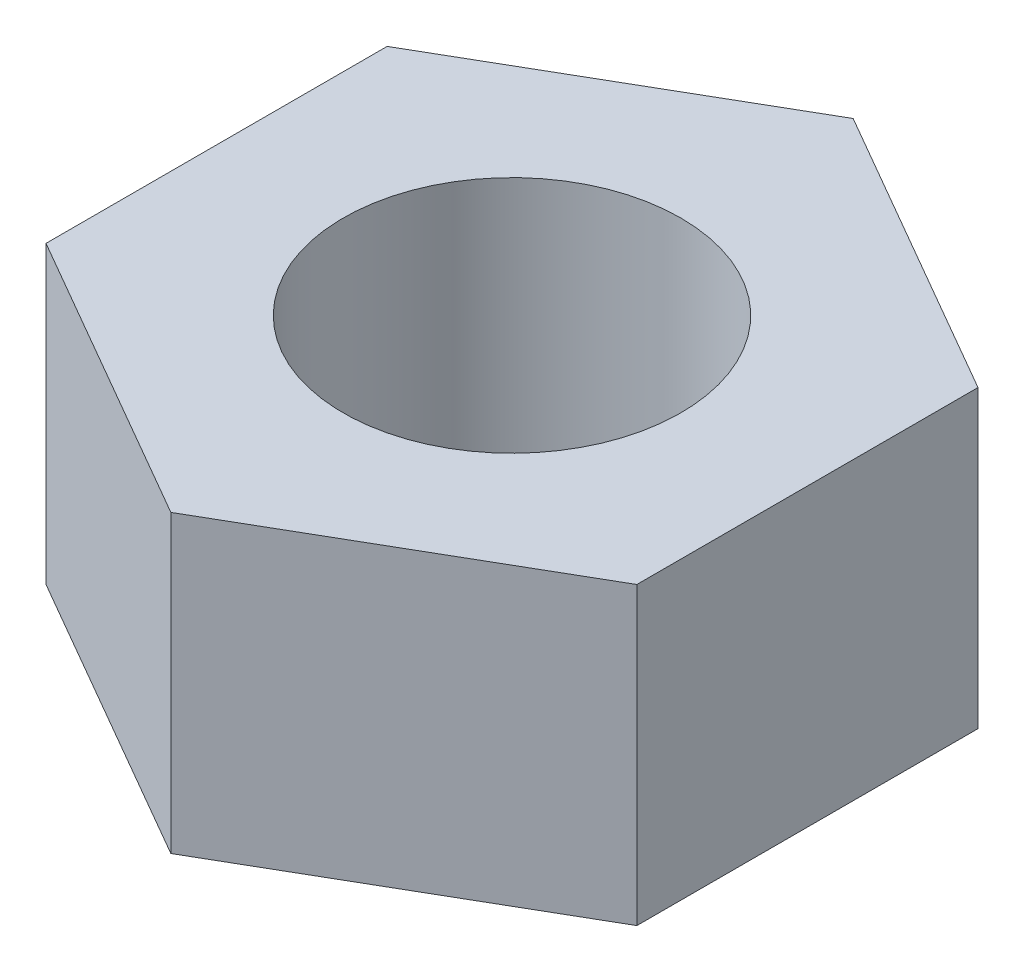
SolidWorks part; units mm, degrees
material "AISI 4130 Steel, normalized at 870C"
ref_plane "Front Plane" through (0, 0, 0) normal (0, 0, 1) x (1, 0, 0)
ref_plane "Top Plane" through (0, 0, 0) normal (0, 1, 0) x (1, 0, 0)
ref_plane "Right Plane" through (0, 0, 0) normal (1, 0, 0) x (0, 0, -1)
sketch "Sketch1" plane through (0, 0, 0) normal (0, 0, 1) x (1, 0, 0)
  line L0 (0, -2.7781) -> (0, 2.7781) construction
  line L1 (5.5562, 0) -> (-5.5562, 0) construction
  line L2 (3.175, -2.7781) -> (-3.175, -2.7781) construction
  line L3 (3.175, -2.7781) -> (3.175, -1.5081) construction
  point P4 (0, 0)
  point P8 (0, 0)
  point P11 (0, -2.7781)
  dimension "Height" = 5.5562
  dimension "Width" = 11.1125
  dimension "Thread Size" = 6.35
  dimension "Thread Pitch" = 1.27
sketch "Sketch2" plane through (0, 0, 0) normal (1, 0, 0) x (0, 0, -1)
  line L0 (0, -2.7781) -> (0, 2.7781) construction
  line L1 (3.048, -3.3433) -> (-3.048, -3.3433)
  line L2 (3.048, -3.3433) -> (3.048, 2.7781)
  line L3 (3.048, 2.7781) -> (-3.048, 2.7781)
  line L4 (-3.048, -3.3433) -> (-3.048, 2.7781)
  line L5 (3.048, -3.3433) -> (-3.048, 2.7781) construction
  line L6 (3.048, 2.7781) -> (-3.048, -3.3433) construction
  point P0 (0, -0.2826)
  point P7 (0, 2.7781)
  dimension "Minimum Slot Width" = 6.096
  dimension "Minimum Slot Depth" = 6.1214
sketch "Sketch11" plane through (0, 0, 0) normal (0, 1, 0) x (1, 0, 0)
  line L1 (0, 6.4158) -> (-5.5562, 3.2079)
  line L2 (-5.5562, 3.2079) -> (-5.5562, -3.2079)
  line L3 (-5.5562, -3.2079) -> (0, -6.4158)
  line L4 (0, -6.4158) -> (5.5562, -3.2079)
  line L5 (5.5562, -3.2079) -> (5.5562, 3.2079)
  line L6 (5.5562, 3.2079) -> (0, 6.4158)
  circle A0 centre (0, 0) radius 5.5563 construction
  circle A1 centre (0, 0) radius 3.175
  point P19 (0, -3.175)
extrude "Boss-Extrude1" add sketch "Sketch11" along normal up to vertex (2.7781 mm away) and the other way up to vertex (2.7781 mm away) up to point (0, 2.7781, 0) other way up to point (0, -2.7781, 0)
fillet "Fillet1" [suppressed] radius 0.3334
sketch "Sketch3" plane through (0, 0, 0) normal (1, 0, 0) x (0, 0, -1)
  line L1 (3.2079, 2.7781) -> (6.4158, 2.7781) construction
  line L2 (5.0006, -2.7781) -> (6.4158, -1.9611)
  line L3 (3.2079, -2.7781) -> (6.4158, -2.7781) construction
  line L4 (6.4158, 2.7781) -> (6.4158, -2.7781) construction
  line L5 (6.4158, -1.9611) -> (6.4158, -2.7781)
  line L7 (5.1118, 2.7781) -> (6.4158, 2.0252)
  line L8 (6.4158, 2.0252) -> (6.4158, 2.7781)
  line L10 (5.0006, -2.7781) -> (6.4158, -2.7781)
  line L12 (5.1118, 0) -> (5.5563, 0) construction
  line L16 (5.1118, 2.7781) -> (6.4158, 2.7781)
  line L21 (3.175, -2.7781) -> (3.175, -2.6194)
  line L22 (-3.2079, -2.7781) -> (3.2079, -2.7781) construction
  line L24 (3.3338, -2.7781) -> (3.175, -2.7781)
  line L25 (3.175, -2.6194) -> (3.3338, -2.7781)
  line L26 (3.175, 2.7781) -> (3.175, 2.6194)
  line L27 (3.175, 2.7781) -> (3.3338, 2.7781)
  line L28 (3.3338, 2.7781) -> (3.175, 2.6194)
  line L29 (3.048, 2.7781) -> (-3.048, 2.7781) construction
  line L30 (3.3338, 0) -> (3.7783, 0) construction
  line L31 (4.6673, 0) -> (5.1118, 0) construction
  line L32 (3.7783, 0) -> (4.2228, 0) construction
  line L33 (4.2228, 0) -> (4.6673, 0) construction
  point P0 (5.1118, 2.7781)
  point P1 (5.5563, 0)
  point P14 (3.175, 0)
  point P36 (5.5563, -2.7781)
  point P44 (5.334, 0)
  dimension "D2" = 30
  dimension "D5" = 0.1588
  dimension "D7" = 0.5556
  dimension "D1" = 30
revolve "Cut-Revolve2" [suppressed] cut sketch "Sketch3" angle 360 about L0
sketch "Sketch15" [suppressed] plane through (16.2719, 0, 15.8104) normal (0.5, 0, -0.866) x (-0.866, 0, -0.5)
  line L0 (21.997, 2.5215) -> (21.997, 1.2768) construction
  line L1 (21.997, -1.2126) -> (21.997, 0.0321) construction
  line L2 (21.997, 0.0321) -> (21.997, 1.2768) construction
  line L3 (21.997, -1.2126) -> (21.997, -2.4573) construction
  line L6 (21.2784, 0.0321) -> (21.6377, -0.5903)
  line L7 (21.6377, -0.5903) -> (22.3564, -0.5903)
  line L8 (22.3564, -0.5903) -> (22.7157, 0.0321)
  line L9 (22.7157, 0.0321) -> (22.3564, 0.6544)
  line L10 (22.3564, 0.6544) -> (21.6377, 0.6544)
  line L11 (21.6377, 0.6544) -> (21.2784, 0.0321)
  circle A0 centre (21.997, 0.0321) radius 0.6224 construction
  spline S4 degree 3 poles (18.7891, 2.0252) (19.8367, 2.3276) (20.9, 2.5208) (22.2636, 2.5217) (22.5377, 2.5101) (23.0797, 2.4648) (23.3489, 2.4312) (24.1517, 2.3016) (24.6805, 2.1766) (25.2049, 2.0252) knots 0 0 0 0 0.5 0.5 0.625 0.625 0.75 0.75 1 1 1 1 construction
  spline S5 degree 3 poles (25.2049, -1.9611) (24.1574, -2.2635) (23.0941, -2.4566) (21.7304, -2.4575) (21.4564, -2.4459) (20.9144, -2.4007) (20.6452, -2.3671) (19.8424, -2.2374) (19.3136, -2.1125) (18.7891, -1.9611) knots 0 0 0 0 0.5 0.5 0.625 0.625 0.75 0.75 1 1 1 1 construction
  point P1 (21.997, 0.6544)
  point P6 (21.997, 0)
extrude "Cut-Extrude2" [suppressed] cut sketch "Sketch15" along normal blind 0.1588
sketch "Sketch18" [suppressed] plane through (0, 2.7781, 0) normal (0, 1, 0) x (1, 0, 0)
  line L0 (0, 0) -> (0, -5.1118) construction
  line L1 (0, 0) -> (-2.9859, -2.9859) construction
  line L2 (0, 0) -> (-1.0929, -4.0789) construction
  line L3 (-5.1118, 0) -> (-4.7562, 0) construction
  line L4 (-4.7562, 0) -> (-4.4006, 0) construction
  line L5 (-4.4006, 0) -> (-4.045, 0) construction
  line L6 (-4.045, 0) -> (-3.6894, 0) construction
  line L7 (-3.6894, 0) -> (-3.3338, 0) construction
  line L8 (0, 0) -> (-2.7781, -4.8119) construction
  line L9 (-5.5562, -3.2079) -> (0, -6.4158) construction
  circle A0 centre (0, 0) radius 5.1118 construction
  circle A1 centre (0, 0) radius 3.3338 construction
  arc A2 (-2.9859, -2.9859) -> (-1.0929, -4.0789) centre (0, 0) ccw construction
  arc A3 (-3.1117, -3.1117) -> (-1.1389, -4.2506) centre (0, 0) ccw
  arc A4 (-2.8602, -2.8602) -> (-1.0469, -3.9071) centre (0, 0) ccw
  arc A5 (-2.8602, -2.8602) -> (-3.1117, -3.1117) centre (-2.9859, -2.9859) ccw
  arc A6 (-1.1389, -4.2506) -> (-1.0469, -3.9071) centre (-1.0929, -4.0789) ccw
  arc A7 (2.9859, -2.9859) -> (1.0929, -4.0789) centre (0, 0) cw construction
  arc A8 (3.1117, -3.1117) -> (1.1389, -4.2506) centre (0, 0) cw
  arc A9 (2.8602, -2.8602) -> (1.0469, -3.9071) centre (0, 0) cw
  arc A10 (2.8602, -2.8602) -> (3.1117, -3.1117) centre (2.9859, -2.9859) cw
  arc A11 (1.1389, -4.2506) -> (1.0469, -3.9071) centre (1.0929, -4.0789) cw
  point P18 (-2.1114, -3.657)
  point P30 (2.1114, -3.657)
  dimension "D1" = 30
extrude "Cut-Extrude3" [suppressed] cut sketch "Sketch18" against normal blind 0.1984
sketch "Sketch5" [suppressed] plane through (0, 0, 0) normal (0, 1, 0) x (1, 0, 0)
  circle A1 centre (0, 0) radius 3.175 construction
  point P0 (0, -3.175)
sketch "Sketch6" [suppressed] plane through (0, 0, 0) normal (0, 0, 1) x (1, 0, 0)
  line L0 (3.175, 2.7781) -> (3.175, -2.7781)
  line L2 (0, -2.7781) -> (5.5562, -2.7781) construction
  line L3 (3.175, -2.7781) -> (0, -2.7781)
  line L4 (0, -2.7781) -> (0, 2.7781)
  line L5 (0, -2.7781) -> (0, 2.7781) construction
  line L6 (0, 2.7781) -> (3.175, 2.7781)
revolve "Revolve2" [suppressed] add sketch "Sketch6" angle 360 about L4
sketch "Sketch7" [suppressed] plane through (0, -2.7781, 0) normal (0, -1, 0) x (1, 0, 0)
  circle A2 centre (0, 0) radius 3.175
  circle A3 centre (0, 0) radius 3.175
  dimension "D1" = 0
curve "Helix/Spiral1" [suppressed] pitch 1.27 height 5.5562 turns 4.375
sketch "Sketch8" [suppressed] plane through (0, 0, 0) normal (0, 0, 1) x (1, 0, 0)
  line L0 (3.3125, -2.6987) -> (2.2126, -3.3337) construction
  line L1 (2.2126, -3.3337) -> (3.3125, -3.9687) construction
  line L2 (3.3125, -3.9687) -> (3.3125, -2.6987) construction
  line L3 (2.3501, -3.2544) -> (2.3501, -3.4131)
  line L4 (3.175, -2.7781) -> (3.175, -3.8894) construction
  line L5 (3.175, -3.3337) -> (3.3125, -3.3337) construction
  line L6 (2.2126, -3.3337) -> (2.3501, -3.3337) construction
  line L7 (3.2437, -3.3337) -> (3.2437, -3.9291) construction
  line L8 (2.3501, -3.2544) -> (3.3125, -2.6987)
  line L9 (3.3125, -2.6987) -> (3.2437, -3.9291)
  line L10 (2.3501, -3.4131) -> (3.2437, -3.9291)
  dimension "D1" = 1.27
  dimension "D2" = 0.1588
sweep "Cut-Sweep1" [suppressed] cut profiles "Sketch8" path "Helix/Spiral1"
sketch "Sketch9" [suppressed] plane through (0, 0, 0) normal (0, 0, 1) x (1, 0, 0)
  line L0 (0, 0.3969) -> (0, -2.7781)
  line L1 (0, 0.3969) -> (0, 0.5556)
  line L2 (0, -2.7781) -> (3.175, -2.7781)
  line L3 (3.175, -2.7781) -> (3.3337, -2.7781)
  line L4 (3.3337, -2.7781) -> (0, 0.5556)
  dimension "D1" = 0.1588
revolve "Revolve3" [suppressed] add sketch "Sketch9" angle 360 about L0
sketch "Sketch14" [suppressed] plane through (0, 0, 0) normal (0, 0, 1) x (1, 0, 0)
  line L0 (3.3337, 2.7781) -> (0, 2.7781)
  line L1 (0, 2.7781) -> (0, -0.5556)
  line L2 (0, -0.5556) -> (3.3337, 2.7781)
revolve "Revolve4" [suppressed] add sketch "Sketch14" angle 360 about L1
sketch "Sketch10" [suppressed] plane through (0, -2.7781, 0) normal (0, -1, 0) x (1, 0, 0)
  circle A0 centre (0, 0) radius 3.3338 construction
  circle A1 centre (0, 0) radius 3.3338
extrude "Boss-Extrude2" [suppressed] add sketch "Sketch10" against normal up to surface (5.5563 mm away) up to face at (0, 2.7781, 0)
combine bodies "Combine1" [suppressed] operation type subtract main body 110 bodies to subtract 120
move or copy body "Body-Move/Copy1" [suppressed] bodies to move or copy 104 parameters "D1"=0, "D2"=0, "D3"=0
move or copy body "Body-Move/Copy2" [suppressed] bodies to move or copy 124 parameters "D1"=0, "D2"=0, "D3"=0
move or copy body "Body-Move/Copy3" [suppressed] bodies to move or copy 125 parameters "D1"=0, "D2"=0, "D3"=0
move or copy body "Body-Move/Copy4" [suppressed] bodies to move or copy 126 parameters "D1"=0, "D2"=0, "D3"=0
move or copy body "Body-Move/Copy5" [suppressed] bodies to move or copy 127 parameters "D1"=0, "D2"=0, "D3"=0
move or copy body "Body-Move/Copy6" [suppressed] bodies to move or copy 128 parameters "D1"=0, "D2"=0, "D3"=0
equation "\"D5@Sketch3\"=\"Thread Size@Sketch1\"*.025"
equation "\"D4@Helix/Spiral1\" = \"Thread Pitch@Sketch1\""
equation "\"D3@Helix/Spiral1\" = \"Height@Sketch1\""
equation "\"D1@Sketch8\" = \"Thread Pitch@Sketch1\""
equation "\"D2@Sketch8\" = \"Thread Pitch@Sketch1\" / 8"
equation "\"D1@Sketch9\"=\"Thread Size@Sketch1\" * .025"
equation "\"D1@Fillet1\"=\"Width@Sketch1\" * .03"
equation "\"D7@Sketch3\"=\"Width@Sketch1\"*.05"
equation "\"D1@Cut-Extrude2\" =  (  ( \"Width@Sketch1\" - \"Thread Size@Sketch1\" / 2 )  * .02 ) "
equation "\"D1@Cut-Extrude3\"=((\"width@sketch1\"-\"Thread Size@sketch1\"/2)*.025)"
